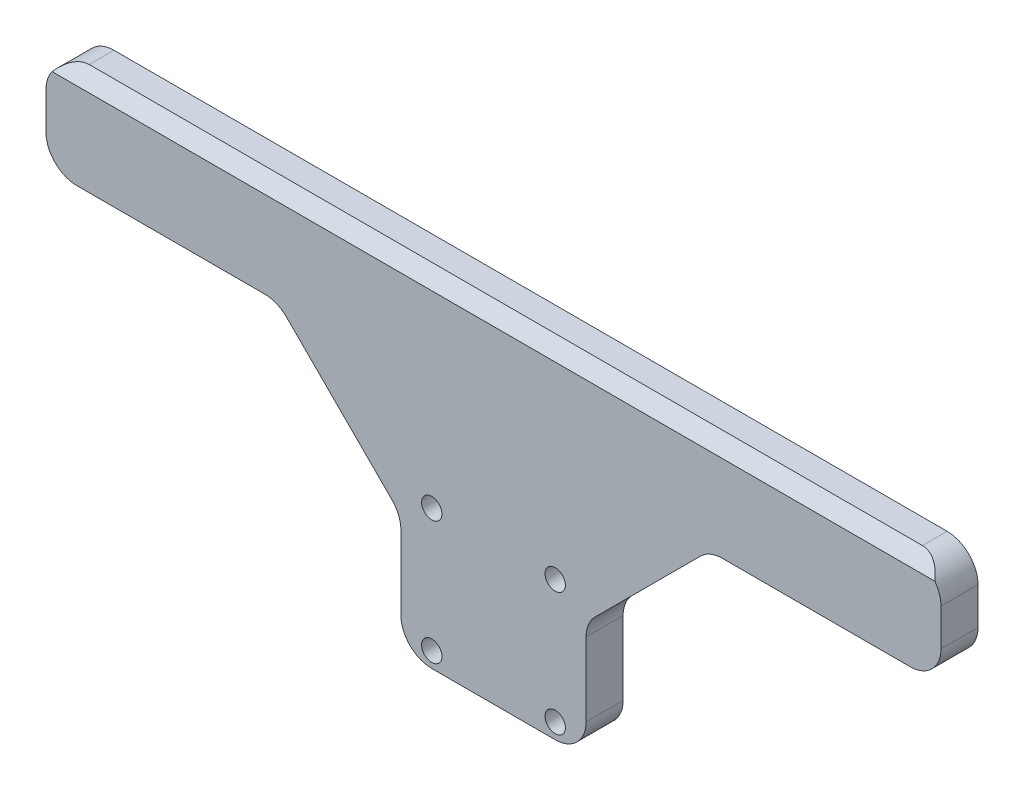
SolidWorks part; units mm, degrees
ref_plane "Front" through (0, 0, 0) normal (0, 0, 1) x (1, 0, 0)
ref_plane "Top" through (0, 0, 0) normal (0, 1, 0) x (1, 0, 0)
ref_plane "Right" through (0, 0, 0) normal (1, 0, 0) x (0, 0, -1)
sketch "Esquisse1" plane through (0, 0, 0) normal (0, 0, 1) x (1, 0, 0)
  line L1 (0, 0) -> (145, 0)
  line L2 (0, 0) -> (0, 25)
  line L3 (0, 25) -> (145, 25)
  line L4 (145, 0) -> (145, 25)
  dimension "D1" = 145
  dimension "D2" = 25
extrude "Boss.-Extru.1" add sketch "Esquisse1" along normal blind 6
sketch "Esquisse2" plane through (0, 0, 6) normal (0, 0, 1) x (1, 0, 0)
  line L0 (72.5, 0) -> (72.5, 25) construction
  line L1 (0, 0) -> (145, 0) construction
  line L2 (145, 25) -> (0, 25) construction
  line L3 (72.5, 12.5) -> (26.2893, 12.5) construction
  circle A0 centre (62.5, 22.5) radius 1.65
  circle A1 centre (62.5, 2.5) radius 1.65
  circle A2 centre (82.5, 2.5) radius 1.65
  circle A3 centre (82.5, 22.5) radius 1.65
  dimension "D1" = 20
  dimension "D2" = 20
  dimension "D3" = 3.3
extrude "Enlèv. mat.-Extru.1" cut sketch "Esquisse2" against normal through all both and the other way through all
sketch "Esquisse3" plane through (0, 0, 6) normal (0, 0, 1) x (1, 0, 0)
  line L0 (145, 0) -> (145, 25) construction
  line L1 (0, 25) -> (145, 25)
  line L2 (0, 25) -> (0, 55)
  line L3 (0, 55) -> (145, 55)
  line L4 (145, 25) -> (145, 55)
  dimension "D1" = 30
extrude "Boss.-Extru.2" add sketch "Esquisse3" against normal up to vertex (6 mm away) up to point (145, 25, 0)
chamfer "Chanfrein1" distance 2 angle 45 1 edges at (72.5, 55, 6)
sketch "Esquisse4" plane through (0, 0, 6) normal (0, 0, 1) x (1, 0, 0)
  line L0 (72.5, 0) -> (72.5, 55) construction
  line L1 (0, 0) -> (57.5, 0)
  line L2 (0, 0) -> (0, 39)
  line L3 (0, 39) -> (57.5, 39)
  line L4 (57.5, 0) -> (57.5, 39)
  line L5 (0, 0) -> (145, 0) construction
  line L6 (0, 55) -> (145, 55) construction
  line L7 (87.5, 0) -> (87.5, 39)
  line L8 (145, 39) -> (87.5, 39)
  line L9 (145, 0) -> (145, 39)
  line L10 (145, 0) -> (87.5, 0)
  dimension "D1" = 30
  dimension "D2" = 16
extrude "Enlèv. mat.-Extru.2" cut sketch "Esquisse4" against normal through all both and the other way through all
chamfer "Chanfrein2" distance 20 angle 45 2 edges at (87.5, 39, 3) (57.5, 39, 3)
fillet "Congé2" radius 5 10 edges at (145, 55, 2) (145, 39, 3) (107.5, 39, 3) (87.5, 19, 3) (87.5, 0, 3) (57.5, 0, 3) (57.5, 19, 3) (37.5, 39, 3) (0, 39, 3) (0, 55, 2)
